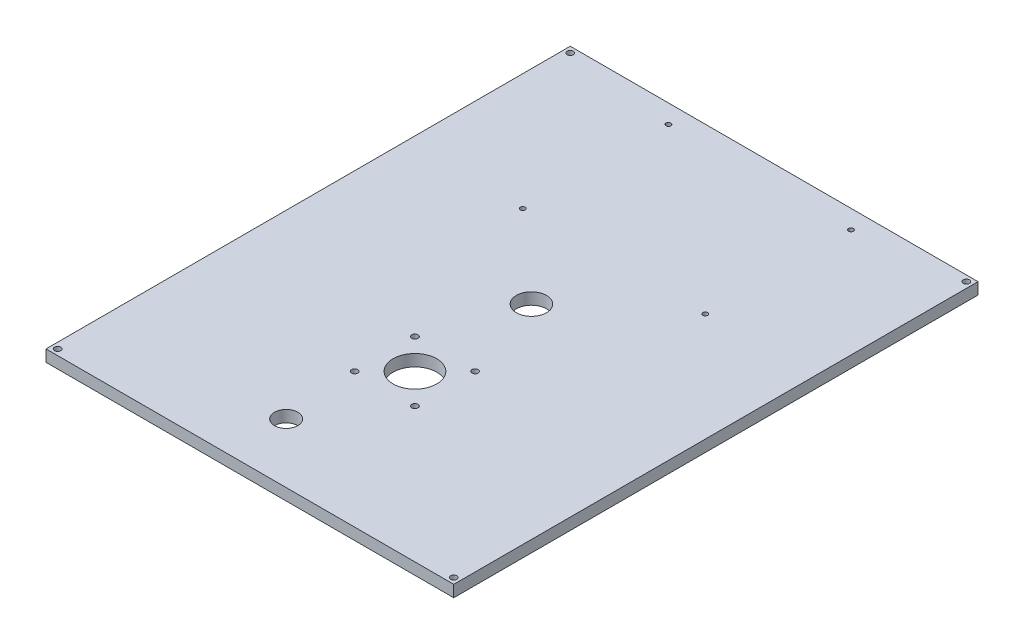
SolidWorks part; units mm, degrees
ref_plane "Front Plane" through (0, 0, 0) normal (0, 0, 1) x (1, 0, 0)
ref_plane "Top Plane" through (0, 0, 0) normal (0, 1, 0) x (1, 0, 0)
ref_plane "Right Plane" through (0, 0, 0) normal (1, 0, 0) x (0, 0, -1)
sketch "Sketch1" plane through (0, 0, 0) normal (0, 1, 0) x (1, 0, 0)
  line L4 (-105, -145) -> (105, -145)
  line L5 (105, -145) -> (105, 125)
  line L6 (105, 125) -> (-105, 125)
  line L7 (-105, 125) -> (-105, -145)
  circle A1 centre (0, 0) radius 7.75
extrude "Boss-Extrude2" add sketch "Sketch1" along normal blind 6
sketch "Sketch3" plane through (0, 0, 0) normal (0, -1, 0) x (1, 0, 0)
  line L0 (0, 60) -> (0, 0) construction
  line L2 (15.5, 44.5) -> (-15.5, 44.5) construction
  line L3 (15.5, 44.5) -> (15.5, 75.5) construction
  line L4 (15.5, 75.5) -> (-15.5, 75.5) construction
  line L5 (-15.5, 44.5) -> (-15.5, 75.5) construction
  line L6 (15.5, 44.5) -> (-15.5, 75.5) construction
  line L7 (15.5, 75.5) -> (-15.5, 44.5) construction
  circle A0 centre (0, 60) radius 11.25
  circle A11 centre (-15.5, 44.5) radius 1.6
  circle A12 centre (15.5, 44.5) radius 1.6
  circle A13 centre (15.5, 75.5) radius 1.6
  circle A14 centre (-15.5, 75.5) radius 1.6
  point P13 (0, 0)
  point P14 (-6.1934, 59.6795)
  point P15 (0, 0)
  dimension "D1" = 31
  dimension "D3" = 22.5
  dimension "D5" = 3.2
  dimension "D6" = 3.2
  dimension "D4" = 3.2
  dimension "D7" = 3.2
  dimension "D2" = 31
  dimension "D10" = 60
extrude "Cut-Extrude1" cut sketch "Sketch3" against normal blind 10
sketch "Sketch4" plane through (0, 0, 0) normal (0, -1, 0) x (1, 0, 0)
  circle A0 centre (49.1703, -115.3822) radius 1.25
  circle A1 centre (-44.8297, -115.3822) radius 1.25
  circle A2 centre (49.1703, -40.3822) radius 1.25
  circle A3 centre (-44.8297, -40.3822) radius 1.25
  dimension "D1" = 2.5
extrude "Cut-Extrude2" cut sketch "Sketch4" against normal blind 10
sketch "Sketch5" plane through (0, 6, 0) normal (0, 1, 0) x (1, 0, 0)
  circle A0 centre (-11.9275, -114.3873) radius 6
extrude "Cut-Extrude3" cut sketch "Sketch5" against normal blind 10
sketch "Sketch6" plane through (0, 0, 0) normal (0, -1, 0) x (1, 0, 0)
  circle A0 centre (102, -122) radius 1.6
  circle A1 centre (102, 142) radius 1.6
  circle A2 centre (-102, 142) radius 1.6
  circle A3 centre (-102, -122) radius 1.6
  dimension "D1" = 3.2
extrude "Cut-Extrude4" cut sketch "Sketch6" against normal blind 10
